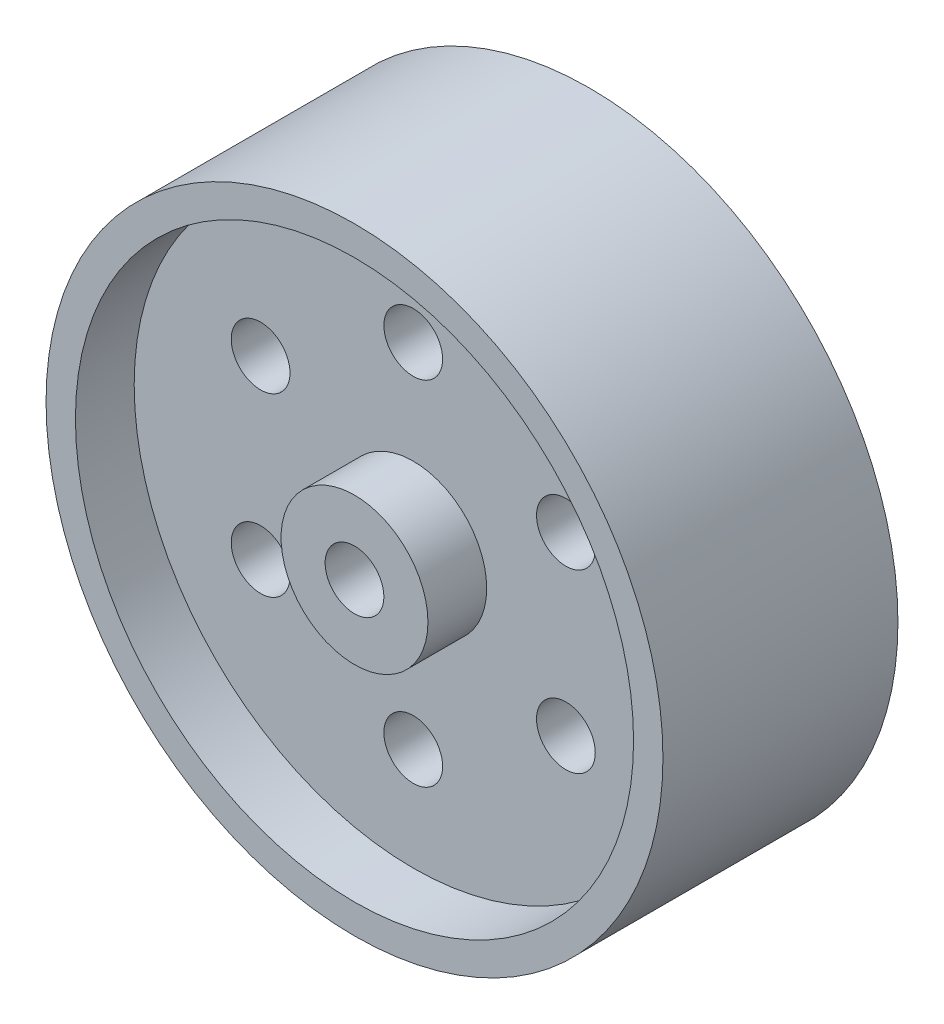
SolidWorks part; units mm, degrees
note: The reader was unsure of these and kept them because the rebuilt part matched: shared geometry of "Sketch1<3>", "Sketch1<4>", "Sketch1<6>", "Sketch1<7>", "Sketch1<8>".
ref_plane "Front Plane" through (0, 0, 0) normal (0, 0, 1) x (1, 0, 0)
ref_plane "Top Plane" through (0, 0, 0) normal (0, 1, 0) x (1, 0, 0)
ref_plane "Right Plane" through (0, 0, 0) normal (1, 0, 0) x (0, 0, -1)
sketch "Sketch1" plane through (0, 0, 0) normal (0, 0, 1) x (1, 0, 0)
  line L0 (0, 31.3007) -> (0, -31.3007) construction
  circle A0 centre (0, 0) radius 2
  circle A1 centre (0, 0) radius 5
  circle A2 centre (0, 0) radius 12 construction
  circle A3 centre (0, 0) radius 15
  circle A4 centre (0, 0) radius 19
  circle A5 centre (0, 0) radius 21
  circle A6 centre (0, 12) radius 2
  circle A7 centre (10.3923, 6) radius 2
  circle A8 centre (10.3923, -6) radius 2
  circle A9 centre (0, -12) radius 2
  circle A10 centre (-10.3923, -6) radius 2
  circle A11 centre (-10.3923, 6) radius 2
  point P4 (0, 0)
  point P15 (0, 0)
  point P26 (0, 0)
  dimension "D1" = 24
  dimension "D2" = 4
  dimension "D3" = 10
  dimension "D4" = 30
  dimension "D5" = 38
  dimension "D6" = 42
  dimension "D7" = 4
  dimension "D8" = 6
extrude "Boss-Extrude1" add sketch "Sketch1" against normal blind 8 contours A4 A3 | A5 A4 | A3 A11 A10 A9 A8 A7 A6 A0
extrude "Boss-Extrude2" add sketch "Sketch1<3>" along normal blind 4 contours A5 A4
sketch "Sketch1<3>" plane through (0, 0, 0) normal (0, 0, 1) x (1, 0, 0) same geometry as "Sketch1"
extrude "Boss-Extrude3" add sketch "Sketch1<4>" against normal blind 12 contours A5 A4 | A4 A3
sketch "Sketch1<4>" plane through (0, 0, 0) normal (0, 0, 1) x (1, 0, 0) same geometry as "Sketch1"
extrude "Boss-Extrude4" add sketch "Sketch1<6>" along normal blind 4 separate body contours A1 A0
sketch "Sketch1<6>" plane through (0, 0, 0) normal (0, 0, 1) x (1, 0, 0) same geometry as "Sketch1"
extrude "Boss-Extrude5" add sketch "Sketch1<7>" along normal blind 4 contours A1 A0
sketch "Sketch1<7>" plane through (0, 0, 0) normal (0, 0, 1) x (1, 0, 0) same geometry as "Sketch1"
extrude "Boss-Extrude6" add sketch "Sketch1<8>" against normal up to surface (8 mm away) contours A1 A0 up to face at (5, 0, -8)
sketch "Sketch1<8>" plane through (0, 0, 0) normal (0, 0, 1) x (1, 0, 0) same geometry as "Sketch1"
